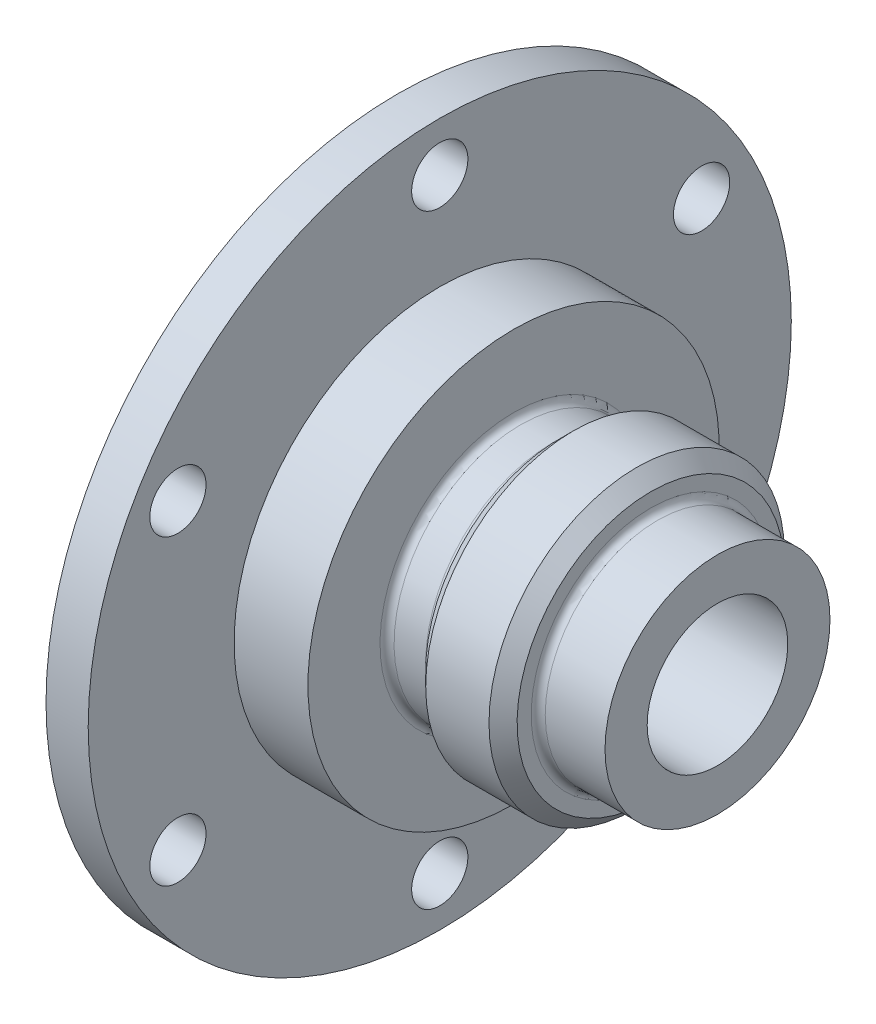
SolidWorks part; units mm, degrees
ref_plane "Front Plane" through (0, 0, 0) normal (0, 0, 1) x (1, 0, 0)
ref_plane "Top Plane" through (0, 0, 0) normal (0, 1, 0) x (1, 0, 0)
ref_plane "Right Plane" through (0, 0, 0) normal (1, 0, 0) x (0, 0, -1)
sketch "Sketch1" plane through (0, 0, 0) normal (0, 0, 1) x (1, 0, 0)
  line L0 (0, 0) -> (0, 50)
  line L1 (0, 50) -> (6, 50)
  line L2 (6, 50) -> (6, 29.25)
  line L3 (6, 29.25) -> (16.5, 29.25)
  line L4 (16.5, 29.25) -> (16.5, 18)
  line L5 (16.5, 18) -> (23, 18)
  line L6 (23, 18) -> (23, 21)
  line L7 (23, 21) -> (36, 21)
  line L8 (36, 21) -> (36, 16)
  line L9 (36, 16) -> (45.5, 16)
  line L10 (45.5, 16) -> (45.5, 0)
  line L11 (45.5, 0) -> (0, 0)
  dimension "D1" = 50
  dimension "D2" = 29.25
  dimension "D3" = 6
  dimension "D4" = 16.5
  dimension "D5" = 6.5
  dimension "D6" = 21
  dimension "D7" = 9.5
  dimension "D8" = 16
  dimension "D9" = 45.5
  dimension "D10" = 18
revolve "Revolve1" add sketch "Sketch1" angle 360 about L11
sketch "Sketch2" plane through (0, 0, 0) normal (0, 0, 1) x (1, 0, 0)
  line L0 (0, 50) -> (0, -50) construction
  line L1 (0, 0) -> (9.5, 0)
  line L2 (0, 0) -> (0, 22.25)
  line L3 (0, 22.25) -> (9.5, 22.25)
  line L4 (9.5, 0) -> (9.5, 22.25)
  line L5 (45.5, -16) -> (45.5, 16) construction
  line L6 (9.5, 0) -> (45.5, 0)
  line L7 (9.5, 0) -> (9.5, 10)
  line L8 (9.5, 10) -> (45.5, 10)
  line L9 (45.5, 0) -> (45.5, 10)
  dimension "D1" = 9.5
  dimension "D2" = 22.25
  dimension "D3" = 10
revolve "Cut-Revolve1" cut sketch "Sketch2" angle 360 about L1 region at (4.75, 11.125, 0) region at (27.5, 5, 0)
sketch "Sketch3" plane through (0, 0, 0) normal (-1, 0, 0) x (0, 0, 1)
  line L0 (0, 0) -> (0, 50) construction
  circle A0 centre (0, 0) radius 50 construction
  point P6 (0, 0)
  point P7 (0, 0)
  point P8 (0, 43)
  point P9 (37.2391, 21.5)
  point P10 (0, 0)
  point P11 (0, 0)
  point P12 (0, 0)
  point P13 (0, 0)
  point P16 (37.2391, -21.5)
  point P17 (0, -43)
  point P18 (-37.2391, -21.5)
  point P19 (-37.2391, 21.5)
  point P20 (0, 0)
  dimension "D1" = 43
  dimension "D2" = 6
  dimension "D3" = 6
hole_wizard "Hole1" positions "Sketch3" profile "Sketch6" legacy end condition through all
sketch "Sketch6" plane through (0, 0, 0) normal (0, 1, 0) x (0, 0, 1)
  line L0 (0, 0) -> (0, 45.5)
  line L1 (0, 45.5) -> (4, 45.5)
  line L2 (4, 45.5) -> (4, 0)
  line L3 (4, 0) -> (0, 0)
  line L4 (0, 110) -> (0, -10) construction
  dimension "Diameter" = 8
  dimension "Depth" = 45.5
chamfer "Chamfer1" distance 2 angle 45 2 edges at (36, 21, 0) (23, 21, 0)
cosmetic thread "Cosmetic Thread1" parameters "D2"=37.066
fillet "Fillet1" radius 1 3 edges at (36, 16, 0) (23, 18, 0) (16.5, 18, 0)
